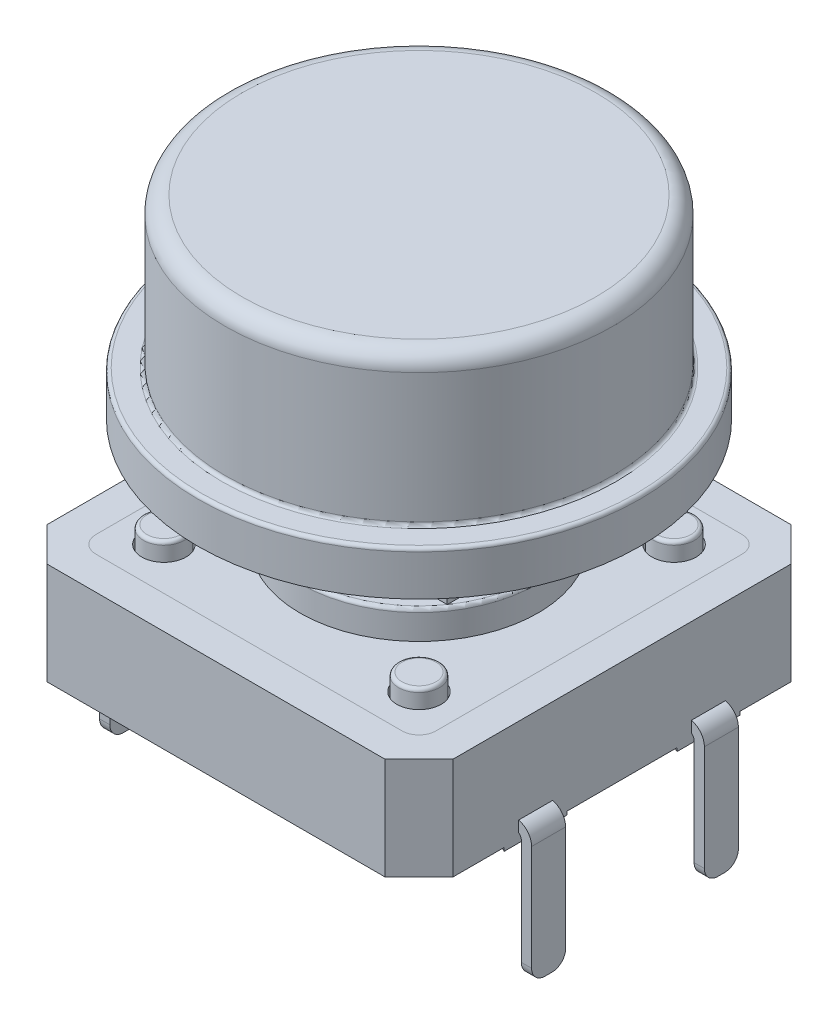
SolidWorks part; units mm, degrees
other "Plastic Button"
other "Button Body"
other "Metal Cover"
other "Connection 2"
other "Connection 1"
ref_plane "Front Plane" through (0, 0, 0) normal (0, 0, 1) x (1, 0, 0)
ref_plane "Top Plane" through (0, 0, 0) normal (0, 1, 0) x (1, 0, 0)
ref_plane "Right Plane" through (0, 0, 0) normal (1, 0, 0) x (0, 0, -1)
sketch "Sketch1" plane through (0, 0, 0) normal (0, 1, 0) x (1, 0, 0)
  line L0 (-5.97, 0) -> (5.97, 0) construction
  line L1 (-5.97, 5.97) -> (5.97, 5.97)
  line L2 (-5.97, 5.97) -> (-5.97, -5.97)
  line L3 (-5.97, -5.97) -> (5.97, -5.97)
  line L4 (5.97, 5.97) -> (5.97, -5.97)
  line L6 (-6.35, 2.54) -> (6.35, 2.54) construction
  line L7 (-6.35, 2.54) -> (-6.35, -2.54) construction
  line L8 (-6.35, -2.54) -> (6.35, -2.54) construction
  line L9 (6.35, 2.54) -> (6.35, -2.54) construction
  line L10 (-6.35, 2.54) -> (6.35, -2.54) construction
  line L11 (-6.35, -2.54) -> (6.35, 2.54) construction
  circle A0 centre (-6.35, 2.54) radius 1 construction
  circle A1 centre (6.35, 2.54) radius 1 construction
  circle A2 centre (6.35, -2.54) radius 1 construction
  circle A3 centre (-6.35, -2.54) radius 1 construction
  point P6 (0, 0)
  dimension "D5" = 2
  dimension "D1" = 11.94
  dimension "D2" = 11.94
  dimension "D3" = 12.7
  dimension "D4" = 5.08
extrude "Boss-Extrude1" add sketch "Sketch1" against normal blind 3
sketch "Sketch2" plane through (0, 0, 0) normal (0, 1, 0) x (1, 0, 0)
  line L1 (-5, 5) -> (5, 5)
  line L2 (-5, 5) -> (-5, -5)
  line L3 (-5, -5) -> (5, -5)
  line L4 (5, 5) -> (5, -5)
  line L5 (-5, 5) -> (5, -5) construction
  line L6 (-5, -5) -> (5, 5) construction
  point P0 (0, 0)
  dimension "D1" = 10
extrude "Cut-Extrude1" cut sketch "Sketch2" against normal blind 0.5
fillet "Fillet1" radius 0.5 4 edges at (-5, -0.25, 5) (5, -0.25, 5) (5, -0.25, -5) (-5, -0.25, -5)
chamfer "Chamfer1" distance 1 angle 45 4 edges at (5.97, -1.5, -5.97) (-5.97, -1.5, -5.97) (-5.97, -1.5, 5.97) (5.97, -1.5, 5.97)
sketch "Sketch3" plane through (0, -0.5, 0) normal (0, 1, 0) x (1, 0, 0)
  line L4 (-5, 4.5) -> (-5, -4.5)
  line L5 (-4.5, -5) -> (4.5, -5)
  line L6 (5, -4.5) -> (5, 4.5)
  line L7 (4.5, 5) -> (-4.5, 5)
  line L8 (-5, 4.5) -> (-5, -4.5)
  line L9 (-4.5, -5) -> (4.5, -5)
  line L10 (5, -4.5) -> (5, 4.5)
  line L11 (4.5, 5) -> (-4.5, 5)
  arc A4 (-5, -4.5) -> (-4.5, -5) centre (-4.5, -4.5) ccw
  arc A5 (4.5, -5) -> (5, -4.5) centre (4.5, -4.5) ccw
  arc A6 (5, 4.5) -> (4.5, 5) centre (4.5, 4.5) ccw
  arc A7 (-4.5, 5) -> (-5, 4.5) centre (-4.5, 4.5) ccw
  arc A8 (-5, -4.5) -> (-4.5, -5) centre (-4.5, -4.5) ccw
  arc A9 (4.5, -5) -> (5, -4.5) centre (4.5, -4.5) ccw
  arc A10 (5, 4.5) -> (4.5, 5) centre (4.5, 4.5) ccw
  arc A11 (-4.5, 5) -> (-5, 4.5) centre (-4.5, 4.5) ccw
  dimension "D1" = 0
extrude "Boss-Extrude2" add sketch "Sketch3" along normal blind 0.5 separate body
sketch "Sketch4" plane through (0, 0, 0) normal (0, 1, 0) x (1, 0, 0)
  line L1 (-3.75, 3.75) -> (3.75, 3.75) construction
  line L2 (-3.75, 3.75) -> (-3.75, -3.75) construction
  line L3 (-3.75, -3.75) -> (3.75, -3.75) construction
  line L4 (3.75, 3.75) -> (3.75, -3.75) construction
  line L5 (-3.75, 3.75) -> (3.75, -3.75) construction
  line L6 (-3.75, -3.75) -> (3.75, 3.75) construction
  circle A0 centre (0, 0) radius 3.5
  circle A1 centre (-3.75, 3.75) radius 0.65
  circle A2 centre (3.75, 3.75) radius 0.65
  circle A3 centre (3.75, -3.75) radius 0.65
  circle A4 centre (-3.75, -3.75) radius 0.65
  dimension "D1" = 7.5
  dimension "D2" = 7
  dimension "D3" = 1.3
extrude "Cut-Extrude2" cut sketch "Sketch4" against normal up to surface (0.5 mm away) up to face at (0, -0.5, 0)
sketch "Sketch5" plane through (0, -0.5, 0) normal (0, 1, 0) x (1, 0, 0)
  circle A0 centre (0, 0) radius 3.45 construction
  circle A1 centre (-3.75, 3.75) radius 0.6
  circle A2 centre (3.75, 3.75) radius 0.6
  circle A3 centre (3.75, -3.75) radius 0.6
  circle A4 centre (-3.75, -3.75) radius 0.6
  dimension "D1" = 6.9
  dimension "D2" = 1.2
extrude "Boss-Extrude3" add sketch "Sketch5" along normal blind 1
sketch "Sketch6" plane through (0, -0.5, 0) normal (0, 1, 0) x (1, 0, 0)
  circle A0 centre (0, 0) radius 3.45 construction
  circle A1 centre (0, 0) radius 3.45
extrude "Boss-Extrude4" add sketch "Sketch6" along normal blind 1.3
sketch "Sketch7" plane through (0, 0.8, 0) normal (0, 1, 0) x (1, 0, 0)
  line L1 (-1.35, 1.35) -> (1.35, 1.35)
  line L2 (-1.35, 1.35) -> (-1.35, -1.35)
  line L3 (-1.35, -1.35) -> (1.35, -1.35)
  line L4 (1.35, 1.35) -> (1.35, -1.35)
  line L5 (-1.35, 1.35) -> (1.35, -1.35) construction
  line L6 (-1.35, -1.35) -> (1.35, 1.35) construction
  point P0 (0, 0)
  dimension "D1" = 2.7
extrude "Boss-Extrude5" add sketch "Sketch7" along normal blind 1.3
sketch "Sketch8" plane through (0, 2.1, 0) normal (0, 1, 0) x (1, 0, 0)
  line L0 (0, 1.925) -> (0, -1.925) construction
  line L1 (-1.725, 1.925) -> (1.725, 1.925)
  line L2 (-1.925, 1.725) -> (-1.925, -1.725)
  line L3 (-1.725, -1.925) -> (1.725, -1.925)
  line L4 (1.925, 1.725) -> (1.925, -1.725)
  arc A0 (-1.725, 1.925) -> (-1.925, 1.725) centre (-1.725, 1.725) ccw
  arc A1 (-1.925, -1.725) -> (-1.725, -1.925) centre (-1.725, -1.725) ccw
  arc A2 (1.725, -1.925) -> (1.925, -1.725) centre (1.725, -1.725) ccw
  arc A3 (1.725, 1.925) -> (1.925, 1.725) centre (1.725, 1.725) cw
  dimension "D3" = 0.2
  dimension "D1" = 3.85
  dimension "D2" = 3.85
extrude "Boss-Extrude6" add sketch "Sketch8" along normal blind 2.1
sketch "Sketch9" plane through (0, 4.2, 0) normal (0, 1, 0) x (1, 0, 0)
  circle A0 centre (0, 0) radius 1
  dimension "D1" = 2
extrude "Cut-Extrude3" cut sketch "Sketch9" against normal blind 1.5
sketch "Sketch10" plane through (0, 0, 0) normal (1, 0, 0) x (0, 0, -1)
  line L0 (0, 0) -> (0, -3) construction
  line L1 (-4.97, -3) -> (4.97, -3) construction
  line L2 (0, 0) -> (0, 3.2) construction
  line L3 (0, 3.2) -> (-6.5, 3.2)
  line L4 (-6.5, 3.2) -> (-6.5, 4.4)
  line L5 (-6.4, 4.5) -> (-5.7, 4.5)
  line L6 (-5.7, 4.5) -> (-5.7, 8.4)
  line L7 (-5.2, 8.9) -> (0, 8.9)
  line L8 (0, 8.9) -> (0, 3.2)
  arc A0 (-5.7, 8.4) -> (-5.2, 8.9) centre (-5.2, 8.4) cw
  arc A1 (-6.5, 4.4) -> (-6.4, 4.5) centre (-6.4, 4.4) cw
  dimension "D1" = 6.5
  dimension "D6" = 0.5
  dimension "D7" = 0.1
  dimension "D2" = 5.7
  dimension "D3" = 1.3
  dimension "D4" = 3.2
  dimension "D5" = 5.7
revolve "Revolve1" add sketch "Sketch10" angle 360 about L8
sketch "Sketch11" plane through (0, 3.2, 0) normal (0, -1, 0) x (1, 0, 0)
  circle A0 centre (0, 0) radius 5
  dimension "D1" = 10
extrude "Cut-Extrude4" cut sketch "Sketch11" against normal blind 4
sketch "Sketch12" plane through (0, 7.2, 0) normal (0, -1, 0) x (1, 0, 0)
  line L0 (-1.55, 0) -> (1.55, 0) construction
  line L2 (1.55, 1.92) -> (2.75, 1.92)
  line L3 (1.55, 1.92) -> (1.55, -1.92)
  line L4 (1.55, -1.92) -> (2.75, -1.92)
  line L5 (2.75, 1.92) -> (2.75, -1.92)
  line L6 (-1.55, 1.92) -> (-2.75, 1.92)
  line L7 (-1.55, 1.92) -> (-1.55, -1.92)
  line L8 (-1.55, -1.92) -> (-2.75, -1.92)
  line L9 (-2.75, 1.92) -> (-2.75, -1.92)
  dimension "D1" = 5.5
  dimension "D2" = 3.84
  dimension "D3" = 1.2
extrude "Boss-Extrude7" add sketch "Sketch12" along normal offset from surface (6.4 mm away) 2.4 up to face at (0, 3.2, -5) offset beyond the face yes
sketch "Sketch13" plane through (0, 0, 1.92) normal (0, 0, 1) x (1, 0, 0)
  line L0 (-1.55, 0.8) -> (-1.55, 7.2) construction
  line L1 (-1.55, 2) -> (-2.05, 2)
  line L2 (-1.55, 2) -> (-1.55, 7.2)
  line L3 (-1.55, 7.2) -> (-2.05, 7.2)
  line L4 (-2.05, 2) -> (-2.05, 7.2)
  line L5 (-5, 7.2) -> (5, 7.2) construction
  line L6 (1.55, 0.8) -> (1.55, 7.2) construction
  line L7 (1.55, 2) -> (2.05, 2)
  line L8 (1.55, 2) -> (1.55, 7.2)
  line L9 (1.55, 7.2) -> (2.05, 7.2)
  line L10 (2.05, 2) -> (2.05, 7.2)
  line L11 (-2.75, 0.8) -> (-1.55, 0.8) construction
  line L12 (-2.75, 0.8) -> (-2.75, 7.2) construction
  dimension "D1" = 0.7
  dimension "D2" = 1.2
extrude "Cut-Extrude5" cut sketch "Sketch13" against normal up to surface (3.84 mm away) up to face at (-2.15, 4, -1.92)
fillet "Fillet2" radius 0.5 2 edges at (-1.55, 0.8, 0) (1.55, 0.8, 0)
fillet "Fillet3" radius 0.6 2 edges at (1.55, 2, 0) (-1.55, 2, 0)
fillet "Fillet4" radius 0.1 5 edges at (0, 0.8, 3.45) (-3.75, 0.5, 4.35) (3.75, 0.5, 4.35) (3.75, 0.5, -3.15) (-3.75, 0.5, -3.15)
sketch "Sketch14" plane through (0, 7.2, 0) normal (0, -1, 0) x (1, 0, 0)
  line L0 (0, 1.93) -> (0, -1.93) construction
  line L2 (-1, 2.75) -> (1, 2.75)
  line L3 (-1, 2.75) -> (-1, 1.93)
  line L4 (-1, 1.93) -> (1, 1.93)
  line L5 (1, 2.75) -> (1, 1.93)
  line L10 (-1, -1.93) -> (1, -1.93)
  line L11 (-1, -1.93) -> (-1, -2.75)
  line L12 (-1, -2.75) -> (1, -2.75)
  line L13 (1, -1.93) -> (1, -2.75)
  dimension "D1" = 2
  dimension "D2" = 0.82
  dimension "D3" = 5.5
extrude "Boss-Extrude8" add sketch "Sketch14" along normal blind 5.36
fillet "Fillet5" radius 0.1 1 edges at (0, 4.5, 5.7)
sketch "Sketch15" plane through (0, 7.2, 0) normal (0, -1, 0) x (1, 0, 0)
  line L0 (0, -2.75) -> (0, 2.75) construction
  line L1 (1, 2.75) -> (-1, 2.75) construction
  line L2 (2.75, 0) -> (-2.75, 0) construction
  line L3 (-0.3, 5.25) -> (0.3, 5.25)
  line L4 (-0.3, 5.25) -> (-0.3, 2.75)
  line L5 (-0.3, 2.75) -> (0.3, 2.75)
  line L6 (0.3, 5.25) -> (0.3, 2.75)
  line L7 (-0.3, -2.75) -> (0.3, -2.75)
  line L8 (-0.3, -2.75) -> (-0.3, -5.25)
  line L9 (-0.3, -5.25) -> (0.3, -5.25)
  line L10 (0.3, -2.75) -> (0.3, -5.25)
  line L11 (2.75, -1.92) -> (2.75, 1.92) construction
  line L13 (2.75, 0.3) -> (5.25, 0.3)
  line L14 (2.75, 0.3) -> (2.75, -0.3)
  line L15 (2.75, -0.3) -> (5.25, -0.3)
  line L16 (5.25, 0.3) -> (5.25, -0.3)
  line L17 (-2.75, 0.3) -> (-5.25, 0.3)
  line L18 (-2.75, 0.3) -> (-2.75, -0.3)
  line L19 (-2.75, -0.3) -> (-5.25, -0.3)
  line L20 (-5.25, 0.3) -> (-5.25, -0.3)
  dimension "D1" = 2.5
  dimension "D2" = 0.6
extrude "Boss-Extrude9" add sketch "Sketch15" along normal up to surface (4 mm away) up to face at (0, 3.2, -5)
ref_plane "Plane1" through (0, 0, 2.54) normal (0, 0, 1) x (1, 0, 0)
sketch "Sketch16" plane through (0, 0, 2.54) normal (0, 0, 1) x (1, 0, 0)
  line L0 (0, 0) -> (0, -2.5) construction
  line L1 (-4.97, 0) -> (4.97, 0) construction
  line L2 (-5.85, -2.5) -> (5.85, -2.5)
  line L3 (0, -2.5) -> (0, -3) construction
  line L4 (-4.97, -3) -> (4.97, -3) construction
  line L5 (6.35, -3) -> (6.35, -6.5)
  line L6 (6.35, -6.5) -> (6.05, -6.5)
  line L7 (6.05, -6.5) -> (6.05, -3)
  line L8 (5.85, -2.8) -> (-5.85, -2.8)
  line L9 (-6.05, -3) -> (-6.05, -6.5)
  line L10 (-6.05, -6.5) -> (-6.35, -6.5)
  line L11 (-6.35, -6.5) -> (-6.35, -3)
  arc A0 (-5.85, -2.8) -> (-6.05, -3) centre (-5.85, -3) ccw
  arc A1 (6.05, -3) -> (5.85, -2.8) centre (5.85, -3) ccw
  arc A2 (-5.85, -2.5) -> (-6.35, -3) centre (-5.85, -3) ccw
  arc A3 (5.85, -2.5) -> (6.35, -3) centre (5.85, -3) cw
  dimension "D5" = 0.2
  dimension "D6" = 0.5
  dimension "D1" = 0.5
  dimension "D2" = 0.3
  dimension "D3" = 0.3
  dimension "D4" = 4
  dimension "D7" = 12.7
extrude "Boss-Extrude10" add sketch "Sketch16" along normal mid plane 1 separate body
mirror "Mirror1" about plane through (0, 0, 0) normal (0, 0, 1) of bodies 116
sketch "Sketch18" plane through (0, -3, 0) normal (0, -1, 0) x (1, 0, 0)
  line L0 (-5.97, -4.97) -> (-5.97, 4.97) construction
  line L1 (-5.97, -3.465) -> (-5.97, -1.615)
  line L2 (5.97, 4.97) -> (5.97, -4.97) construction
  line L3 (5.97, 3.465) -> (5.97, 1.615)
  line L4 (5.97, -1.615) -> (5.97, -3.465)
  line L5 (-5.97, 1.615) -> (-5.97, 3.465)
  line L6 (-5, 0) -> (5, 0) construction
  line L7 (-3, 5) -> (3, 5)
  line L8 (-5, 3) -> (-5, -3)
  line L9 (-3, -5) -> (3, -5)
  line L10 (5, 3) -> (5, -3)
  circle A0 centre (-6.35, 2.54) radius 1 construction
  arc A1 (-5.97, 1.615) -> (-5.97, 3.465) centre (-6.35, 2.54) ccw
  circle A2 centre (6.35, 2.54) radius 1 construction
  arc A3 (5.97, 3.465) -> (5.97, 1.615) centre (6.35, 2.54) ccw
  circle A4 centre (-6.35, -2.54) radius 1 construction
  arc A5 (-5.97, -3.465) -> (-5.97, -1.615) centre (-6.35, -2.54) ccw
  circle A6 centre (6.35, -2.54) radius 1 construction
  arc A7 (5.97, -1.615) -> (5.97, -3.465) centre (6.35, -2.54) ccw
  arc A8 (-3, 5) -> (-5, 3) centre (-3, 3) ccw
  arc A9 (-5, -3) -> (-3, -5) centre (-3, -3) ccw
  arc A10 (3, -5) -> (5, -3) centre (3, -3) ccw
  arc A11 (3, 5) -> (5, 3) centre (3, 3) cw
  dimension "D3" = 2
  dimension "D1" = 10
  dimension "D2" = 10
extrude "Boss-Extrude12" add sketch "Sketch18" along normal blind 0.1
sketch "Sketch19" plane through (0, -3.1, 0) normal (0, -1, 0) x (1, 0, 0)
  line L0 (-3, 5) -> (-3, 3)
  line L1 (-3, 3) -> (-5, 3)
  line L2 (3, 5) -> (3, 3)
  line L3 (3, 3) -> (5, 3)
  line L4 (-5, 3) -> (-5, -3)
  line L5 (-3, -5) -> (3, -5)
  line L6 (5, -3) -> (5, 3)
  line L7 (3, 5) -> (-3, 5)
  line L8 (-5, 3) -> (-5, -3)
  line L9 (-3, -5) -> (3, -5)
  line L10 (5, -3) -> (5, 3)
  line L11 (3, 5) -> (-3, 5)
  line L12 (-5, -3) -> (-3, -3)
  line L13 (-3, -3) -> (-3, -5)
  line L14 (3, -5) -> (3, -3)
  line L15 (3, -3) -> (5, -3)
  line L17 (-3, 3) -> (3, 3) construction
  line L18 (-3, 3) -> (-3, -3) construction
  line L19 (-3, -3) -> (3, -3) construction
  line L20 (3, 3) -> (3, -3) construction
  line L21 (-3, 3) -> (3, -3) construction
  line L22 (-3, -3) -> (3, 3) construction
  arc A4 (-3, 5) -> (-5, 3) centre (-3, 3) ccw
  arc A5 (-5, -3) -> (-3, -5) centre (-3, -3) ccw
  arc A6 (3, -5) -> (5, -3) centre (3, -3) ccw
  arc A7 (5, 3) -> (3, 5) centre (3, 3) ccw
  point P0 (0, 0)
  point P17 (-2.8454, 3)
  dimension "D1" = 0
extrude "Cut-Extrude6" cut sketch "Sketch19" against normal up to surface (0.1 mm away) up to face at (0, -3, 0)
fillet "Fillet6" radius 0.4 4 edges at (-6.2, -6.5, 3.04) (-6.2, -6.5, 2.04) (6.2, -6.5, 2.04) (6.2, -6.5, 3.04)
fillet "Fillet7" radius 0.4 4 edges at (-6.2, -6.5, -3.04) (-6.2, -6.5, -2.04) (6.2, -6.5, -2.04) (6.2, -6.5, -3.04)
